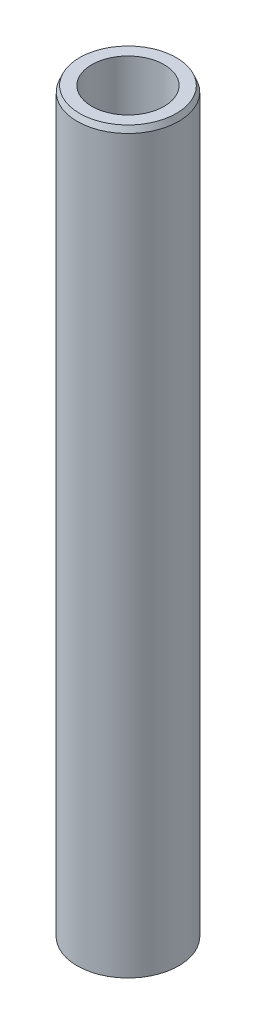
SolidWorks part; units mm, degrees
ref_plane "Front Plane" through (0, 0, 0) normal (0, 0, 1) x (1, 0, 0)
ref_plane "Top Plane" through (0, 0, 0) normal (0, 1, 0) x (1, 0, 0)
ref_plane "Right Plane" through (0, 0, 0) normal (1, 0, 0) x (0, 0, -1)
sketch "Sketch1" plane through (0, 0, 0) normal (0, 1, 0) x (1, 0, 0)
  circle A0 centre (0, 0) radius 35
  dimension "SHAFT_OD" = 70
extrude "Boss-Extrude1" add sketch "Sketch1" along normal blind 509.6987
sketch "Sketch2" plane through (0, 0, 0) normal (0, 1, 0) x (1, 0, 0)
  circle A0 centre (0, 0) radius 24.932
  dimension "BORE_D" = 49.864
extrude "Cut-Extrude1" cut sketch "Sketch2" along normal through all
chamfer "Chamfer1" distance 3.9205 angle 22.89 2 edges at (0, 509.6987, 35) (0, 0, 35) first distance on face at (0, 509.6987, 35) first distance on face at (0, 0, 24.932)
